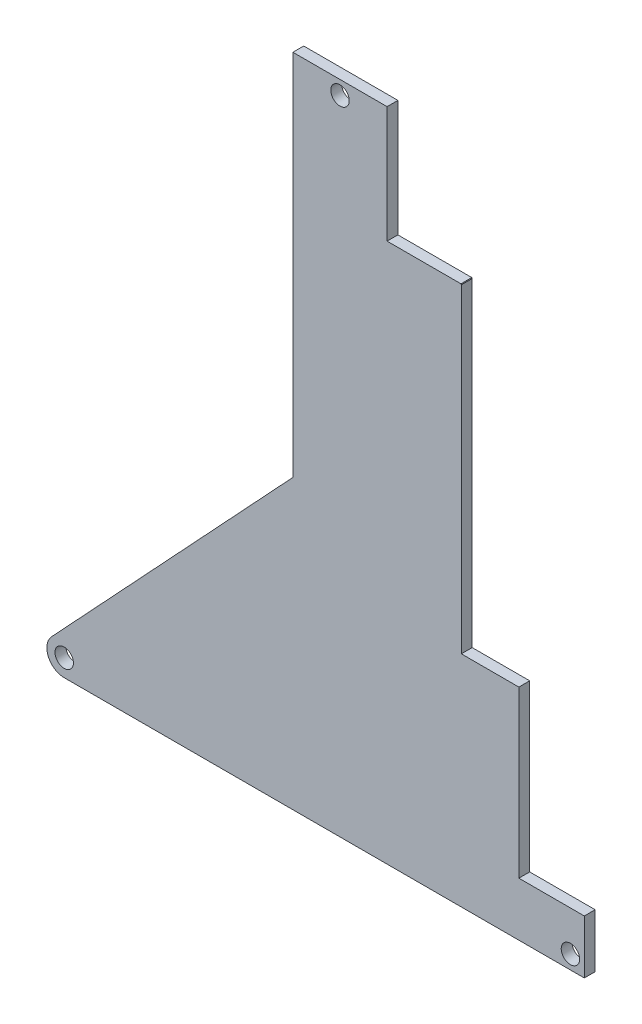
SolidWorks part; units mm, degrees
ref_plane "Front Plane" through (0, 0, 0) normal (0, 0, 1) x (1, 0, 0)
ref_plane "Top Plane" through (0, 0, 0) normal (0, 1, 0) x (1, 0, 0)
ref_plane "Right Plane" through (0, 0, 0) normal (1, 0, 0) x (0, 0, -1)
sketch "Sketch1" plane through (0, 0, 0) normal (0, 0, 1) x (1, 0, 0)
  line L1 (-52.6486, -67.2724) -> (-30.5784, -43.6209)
  line L3 (-30.5784, -43.6209) -> (-18.8373, -31.0385)
  line L4 (-18.8373, 22.9178) -> (-18.8373, 15.0967)
  line L5 (-62.4049, -73.074) -> (-22.4391, -30.2446) construction
  line L6 (-54.2124, -68.9483) -> (-52.6486, -67.2724)
  line L7 (-60.0836, -75.2401) -> (-20.1178, -32.4107) construction
  line L9 (23.8665, -73.2212) -> (-30.5784, -73.2212)
  line L12 (-18.8373, 15.0967) -> (-18.8373, -31.0385)
  line L13 (-30.5784, -73.2212) -> (-52.3554, -73.2212)
  line L14 (-18.8373, 22.9178) -> (-5.0365, 22.9178)
  line L20 (23.8665, -65.3472) -> (23.8665, -73.2212)
  arc A1 (25.454, -65.3472) -> (-3.6178, 23.6674) centre (-125.3585, -65.3472) ccw construction
  arc A2 (23.8665, -65.3472) -> (-5.0365, 22.9178) centre (-125.3585, -65.3472) ccw
  arc A3 (23.8665, -65.3472) -> (-4.8993, 22.7304) centre (-125.3585, -65.3472) ccw construction
  arc A7 (-52.3554, -73.2212) -> (-54.2124, -68.9483) centre (-52.3554, -70.6812) cw
  dimension "D5" = 2.54
  dimension "D1" = 1.5875
  dimension "D2" = 3.175
extrude "Boss-Extrude1" add sketch "Sketch1" along normal blind 1.5875
hole_wizard "#2 Clearance Hole1" positions "Sketch3" profile "Sketch2" hole size "#2" standard "ANSI Inch" end condition through all
sketch "Sketch3" plane through (0, 0, 0) normal (0, 0, -1) x (-1, 0, 0)
  line L0 (11.9369, 20.8858) -> (11.9369, 22.9178) construction
  line L1 (5.0365, 22.9178) -> (18.8373, 22.9178) construction
  line L2 (-23.8665, -73.2212) -> (-23.8665, -65.3472) construction
  line L3 (52.3554, -73.2212) -> (-23.8665, -73.2212) construction
  point P0 (-21.8345, -71.1892)
  point P2 (52.3554, -70.6812)
  point P5 (11.9369, 20.8858)
  dimension "D1" = 2.032
  dimension "D2" = 2.032
  dimension "D3" = 2.032
sketch "Sketch2" plane through (21.8345, -71.1892, 0) normal (1, 0, 0) x (0, 1, 0)
  line L0 (0, 0) -> (0, 1.5875)
  line L1 (0, 1.5875) -> (1.3525, 1.5875)
  line L2 (1.3525, 1.5875) -> (1.3525, 0)
  line L5 (1.3525, 0) -> (0, 0)
  line L11 (0, -6.35) -> (0, 107.95) construction
  dimension "Thru Hole Dia." = 2.7051
  dimension "Thru Hole Depth" = 1.5875
sketch "Sketch4" plane through (0, 0, 0) normal (0, 0, -1) x (-1, 0, 0)
  line L1 (-23.8665, -65.3472) -> (-14.278, -65.3472)
  line L2 (-23.8665, -65.3472) -> (-23.8665, -41.0902)
  line L3 (-23.8665, -41.0902) -> (-14.278, -41.0902)
  line L4 (-14.278, -65.3472) -> (-14.278, -41.0902)
  line L5 (-23.8665, -65.3472) -> (-14.278, -41.0902) construction
  line L6 (-23.8665, -41.0902) -> (-14.278, -65.3472) construction
  line L8 (-14.278, -41.0902) -> (-9.1472, -41.0902) construction
  line L9 (-14.278, -73.9832) -> (-14.278, -41.0902) construction
  line L10 (-5.8452, 5.8452) -> (-21.8817, 5.8452)
  line L11 (-5.8452, 5.8452) -> (-5.8452, -41.0902)
  line L12 (-5.8452, -41.0902) -> (-21.8817, -41.0902)
  line L13 (-21.8817, 5.8452) -> (-21.8817, -41.0902)
  line L14 (-5.8452, 5.8452) -> (-21.8817, -41.0902) construction
  line L15 (-5.8452, -41.0902) -> (-21.8817, 5.8452) construction
  line L16 (5.0365, 22.9178) -> (-5.8452, 22.9178)
  line L17 (5.0365, 22.9178) -> (5.0365, 5.8452)
  line L18 (5.0365, 5.8452) -> (-5.8452, 5.8452)
  line L19 (-5.8452, 22.9178) -> (-5.8452, 5.8452)
  line L20 (5.0365, 22.9178) -> (-5.8452, 5.8452) construction
  line L21 (5.0365, 5.8452) -> (-5.8452, 22.9178) construction
  arc A0 (5.0365, 22.9178) -> (-23.8665, -65.3472) centre (125.3585, -65.3472) ccw construction
  point P4 (-19.0722, -53.2187)
  point P14 (-13.8635, -17.6225)
  point P23 (-0.4043, 14.3815)
  arc M8 (5.0365, 22.9178) -> (-23.8665, -65.3472) centre (125.3585, -65.3472) ccw
extrude "Cut-Extrude1" cut sketch "Sketch4" against normal through all contours L1 L4 L3 M8 | L12 L11 L3 M8 | L18 L17 M8 region at (18.7619, -53.6674, 0) region at (11.7225, -24.2369, 0) region at (-1.3365, 11.675, 0)
sketch "Sketch5" plane through (0, 0, 1.5875) normal (0, 0, 1) x (1, 0, 0)
  line L0 (23.8665, -73.2212) -> (23.8665, -65.3472) construction
  line L1 (-52.3554, -73.2212) -> (23.8665, -73.2212) construction
  line L2 (-18.8373, -31.0385) -> (-54.2124, -68.9483) construction
  line L3 (-18.8373, 22.9178) -> (-18.8373, -31.0385) construction
  line L4 (-5.0365, 22.9178) -> (-18.8373, 22.9178) construction
  line L5 (23.8665, -73.2212) -> (23.8665, -65.3472)
  line L6 (-52.3554, -73.2212) -> (23.8665, -73.2212)
  line L7 (-18.8373, -31.0385) -> (-54.2124, -68.9483)
  line L8 (-18.8373, 22.9178) -> (-18.8373, -31.0385)
  line L9 (-5.0365, 22.9178) -> (-18.8373, 22.9178)
  line L10 (-8.3564, -18.1732) -> (-8.2164, -18.0332) construction
  line L11 (9.0626, -17.9112) -> (7.9226, -16.7712) construction
  line L12 (7.9226, -40.2632) -> (9.0626, -39.1232) construction
  line L13 (0.6896, 0.0546) -> (-0.7604, 2.0546) construction
  line L14 (0.5596, -34.0654) -> (-0.8704, -32.0854) construction
  line L15 (-6.9504, 0.0746) -> (-8.3604, 2.0346) construction
  line L17 (-8.3604, -8.1254) -> (-6.9504, -10.0854) construction
  line L18 (-7.0804, -34.0454) -> (-8.5104, -32.0654) construction
  line L19 (-0.8704, -8.1254) -> (0.5396, -10.0854) construction
  line L21 (-7.0604, -23.9054) -> (-8.5104, -21.9054) construction
  line L23 (-0.8704, -21.9254) -> (0.5596, -23.9054) construction
  arc A1 (-54.2124, -68.9483) -> (-52.3554, -73.2212) centre (-52.3554, -70.6812) ccw construction
  arc A2 (23.8665, -65.3472) -> (-4.8993, 22.7304) centre (-125.3585, -65.3472) ccw
  arc A3 (23.8665, -65.3472) -> (-4.8993, 22.7304) centre (-125.3585, -65.3472) ccw
  arc A4 (-54.2124, -68.9483) -> (-52.3554, -73.2212) centre (-52.3554, -70.6812) ccw
  circle A5 centre (-11.9369, 20.8858) radius 1.3525 construction
  circle A6 centre (-11.9369, 20.8858) radius 1.3525
  circle A7 centre (-52.3554, -70.6812) radius 1.3526 construction
  circle A8 centre (21.8345, -71.1892) radius 1.3525 construction
  circle A9 centre (-52.3554, -70.6812) radius 1.3526
  circle A10 centre (21.8345, -71.1892) radius 1.3526
  circle A19 centre (9.452, -44.697) radius 0.5
  circle A20 centre (0.4604, -44.697) radius 0.5
  circle A21 centre (-8.5312, -44.697) radius 0.5
  circle A22 centre (-17.5228, -44.697) radius 0.5
  circle A23 centre (-26.5144, -44.697) radius 0.5
  circle A24 centre (9.452, -53.2314) radius 0.5
  circle A25 centre (0.4604, -53.2314) radius 0.5
  circle A26 centre (-8.5312, -53.2314) radius 0.5
  circle A27 centre (-17.5228, -53.2314) radius 0.5
  circle A28 centre (-26.5144, -53.2314) radius 0.5
  circle A29 centre (-35.506, -61.842) radius 0.5
  circle A30 centre (-26.5144, -61.842) radius 0.5
  circle A31 centre (-17.5228, -61.842) radius 0.5
  circle A32 centre (-8.5312, -61.842) radius 0.5
  circle A33 centre (0.4604, -61.842) radius 0.5
  circle A34 centre (9.452, -61.842) radius 0.5
  circle A35 centre (9.452, -70.3764) radius 0.5
  circle A36 centre (0.4604, -70.3764) radius 0.5
  circle A37 centre (-8.5312, -70.3764) radius 0.5
  circle A38 centre (-17.5228, -70.3764) radius 0.5
  circle A39 centre (-26.5144, -70.3764) radius 0.5
  circle A40 centre (-35.506, -70.3764) radius 0.5
  circle A41 centre (-4.0354, -4.0354) radius 2.54
  circle A42 centre (-4.0354, -28.0092) radius 2.54
  circle A45 centre (-8.2864, -18.1032) radius 0.8643
  circle A46 centre (-4.0954, -35.3752) radius 2.9693
  circle A47 centre (6.0646, -26.2312) radius 4.1352
  circle A48 centre (8.4926, -17.3412) radius 2.9727
  circle A49 centre (8.4926, -39.6932) radius 1.6278
  circle A50 centre (-7.6554, 1.0546) radius 0.5
  circle A51 centre (-0.0354, 1.0546) radius 0.5
  circle A52 centre (-0.1654, -9.1054) radius 0.5
  circle A53 centre (-7.6554, -9.1054) radius 0.5
  circle A54 centre (-7.7954, -33.0554) radius 0.5
  circle A55 centre (-0.1554, -33.0754) radius 0.5
  circle A56 centre (-0.1554, -22.9154) radius 0.5
  circle A57 centre (-7.7854, -22.9054) radius 0.5
  dimension "D2" = 1
  dimension "D3" = 5.08
  dimension "D1" = 1.5875
